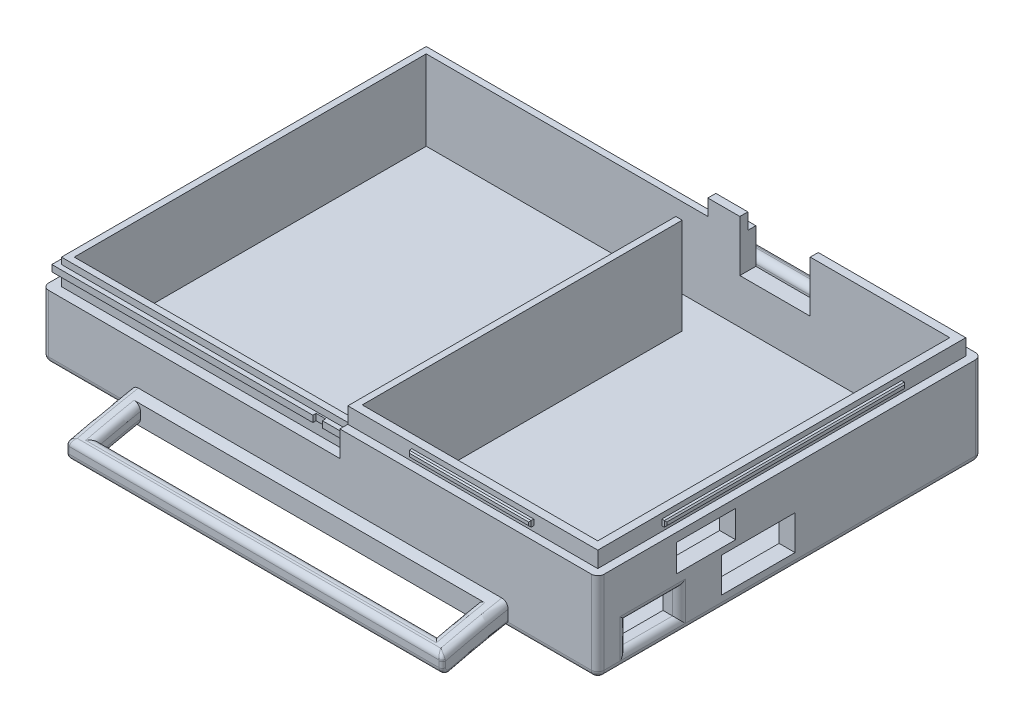
SolidWorks part; units mm, degrees
ref_plane "Front Plane" through (0, 0, 0) normal (0, 0, 1) x (1, 0, 0)
ref_plane "Top Plane" through (0, 0, 0) normal (0, 1, 0) x (1, 0, 0)
ref_plane "Right Plane" through (0, 0, 0) normal (1, 0, 0) x (0, 0, -1)
sketch "Sketch1" plane through (0, 0, 0) normal (0, 1, 0) x (1, 0, 0)
  line L1 (22, -27.5) -> (-22, -27.5)
  line L2 (22, -27.5) -> (22, 27.5)
  line L3 (22, 27.5) -> (-22, 27.5)
  line L4 (-22, -27.5) -> (-22, 27.5)
  line L5 (22, -27.5) -> (-22, 27.5) construction
  line L6 (22, 27.5) -> (-22, -27.5) construction
  line L10 (23, 27.5) -> (23, -27.5)
  line L11 (23, 27.5) -> (59.8, 27.5)
  line L12 (23, -27.5) -> (59.8, -27.5)
  line L13 (59.8, 27.5) -> (59.8, -27.5)
  line L14 (22, 27.5) -> (22, -27.5)
  line L15 (22, 27.5) -> (23, 27.5)
  line L16 (22, -27.5) -> (23, -27.5)
  line L17 (23, 27.5) -> (23, -27.5)
  line L18 (22, -30) -> (-24.5, -30)
  line L19 (-24.5, -30) -> (-24.5, 30)
  line L20 (22, 30) -> (-24.5, 30)
  line L21 (22, 30) -> (23, 30)
  line L22 (23, 30) -> (62.3, 30)
  line L23 (62.3, 30) -> (62.3, -30)
  line L24 (23, -30) -> (62.3, -30)
  line L25 (22, -30) -> (23, -30)
  line L26 (22, 30) -> (22, 27.5)
  line L27 (22, -27.5) -> (22, -30)
  line L29 (22, 27.5) -> (23, 27.5)
  line L30 (22, 27.5) -> (22, -27.5)
  line L31 (22, -27.5) -> (23, -27.5)
  line L32 (23, 27.5) -> (23, -27.5)
  line L33 (22, 27.5) -> (23, 27.5)
  line L34 (22, 27.5) -> (22, 22.5)
  line L35 (22, 22.5) -> (23, 22.5)
  line L36 (23, 27.5) -> (23, 22.5)
  point P0 (0, 0)
  dimension "D1" = 55
  dimension "D2" = 44
  dimension "D3" = 1
  dimension "D4" = 2.5
  dimension "D5" = 86.8
  dimension "D6" = 36.8
  dimension "D7" = 60
  dimension "D8" = 5
extrude "Boss-Extrude1" add sketch "Sketch1" along normal blind 12.5 contours L27 L1 L4 L3 L26 L20 L19 L18 region at (21.2409, 0, 28.75)
extrude "Boss-Extrude2" add sketch "Sketch1<5>" along normal blind 15 contours L16 L27 L25 L24 L23 L22 L21 L26 L15 L11 L13 L12 region at (22.5, 0, 28.2228)
sketch "Sketch1<5>" plane through (0, 0, 0) normal (0, 1, 0) x (1, 0, 0) same geometry as "Sketch1"
extrude "Boss-Extrude3" add sketch "Sketch1<7>" along normal blind 15 contours L2 L16 L10 L15 region at (22.5, 0, 2.5)
sketch "Sketch1<7>" plane through (0, 0, 0) normal (0, 1, 0) x (1, 0, 0) same geometry as "Sketch1"
extrude "Boss-Extrude5" add sketch "Sketch1<10>" against normal blind 1.5 contours L27 L1 L4 L3 L26 L20 L19 L18 | L4 L1 L2 L3 | L13 L11 L10 L12 | L2 L16 L10 L15 | L16 L27 L25 L24 L23 L22 L21 L26 L15 L11 L13 L12 | L30 L35 L10 L15 region at (21.2409, 0, 28.75) region at (0, 0, 0) region at (22.5, 0, 2.5) region at (22.5, 0, 28.2228) region at (22.5, 0, -25) region at (41.4, 0, 0)
sketch "Sketch1<10>" plane through (0, 0, 0) normal (0, 1, 0) x (1, 0, 0) same geometry as "Sketch1"
sketch "Sketch2" plane through (62.3, 0, 0) normal (1, 0, 0) x (0, 0, -1)
  line L0 (-25.5, 0.5) -> (-17.3172, 0.5)
  line L1 (-25.5, 0.5) -> (-25.5, 4.5)
  line L2 (-25.5, 4.5) -> (-17.3172, 4.5)
  line L3 (-17.3172, 0.5) -> (-17.3172, 4.5)
  line L4 (-10.6702, 0.4971) -> (-10.6702, 5.8971)
  line L5 (-10.6702, 5.8971) -> (0.8298, 5.8971)
  line L6 (0.8298, 0.4971) -> (0.8298, 5.8971)
  line L7 (-10.6702, 0.4971) -> (0.8298, 0.4971)
  line L8 (-17.6602, 6.8853) -> (-8.4602, 6.8853)
  line L9 (-17.6602, 6.8853) -> (-17.6602, 11.1353)
  line L10 (-17.6602, 11.1353) -> (-8.4602, 11.1353)
  line L11 (-8.4602, 6.8853) -> (-8.4602, 11.1353)
  line L12 (-30, 15) -> (-30, -1.5) construction
  line L14 (30, -1.5) -> (-30, -1.5) construction
  dimension "D1" = 0.9882
  dimension "D2" = 2.3853
  dimension "D3" = 9.2
  dimension "D4" = 2.21
  dimension "D5" = 0.343
  dimension "D6" = 4.5
  dimension "D7" = 4
  dimension "D8" = 4.25
  dimension "D9" = 2
  dimension "D10" = 11.5
extrude "Side_USB" cut sketch "Sketch2" against normal blind 10
sketch "Sketch3" plane through (0, 0, -30) normal (0, 0, -1) x (-1, 0, 0)
  line L0 (-22, 15) -> (-22, 12.5) construction
  line L1 (-38, 15) -> (-27, 15)
  line L2 (-38, 15) -> (-38, 7)
  line L3 (-38, 7) -> (-27, 7)
  line L4 (-27, 15) -> (-27, 7)
  line L5 (-22, 15) -> (-62.3, 15) construction
  dimension "D1" = 5
  dimension "D2" = 0
  dimension "D3" = 8
  dimension "D4" = 11
extrude "Back_USB" cut sketch "Sketch3" against normal blind 10
sketch "Sketch4" plane through (0, 15, 0) normal (0, 1, 0) x (1, 0, 0)
  line L0 (23.25, -28.75) -> (23.25, 28.75)
  line L1 (22, -30) -> (62.3, -30)
  line L2 (22, -30) -> (22, 30)
  line L3 (22, 30) -> (62.3, 30)
  line L4 (62.3, -30) -> (62.3, 30)
  line L5 (23.25, 28.75) -> (61.05, 28.75)
  line L6 (61.05, -28.75) -> (61.05, 28.75)
  line L7 (23.25, -28.75) -> (61.05, -28.75)
  line L8 (22, 27.5) -> (23.25, 27.5)
  line L9 (59.8, 27.5) -> (-22, 27.5) construction
  line L10 (22, 27.5) -> (27, 27.5) construction
  line L11 (22, -27.5) -> (23.25, -27.5)
  line L12 (59.8, -27.5) -> (23, -27.5) construction
  line L13 (23.25, 28.75) -> (22, 28.75)
  line L14 (23.25, -28.75) -> (22, -28.75)
  line M9 (38, 30) -> (38, 27.5)
  line M15 (22, 22.5) -> (22, -30)
  line M16 (22, -30) -> (62.3, -30)
  line M17 (62.3, -30) -> (62.3, 30)
  line M18 (62.3, 30) -> (38, 30)
  dimension "D1" = 1.25
extrude "Groove" cut sketch "Sketch4" against normal blind 2.5 contours L7 L14 L5 L6 M15 M16 M17 M18 M9 | L13 L5 L3 L2 M9 region at (42.15, 15, 29.4728) region at (30, 15, -29.375)
sketch "LidGrip_Back_Sketch" plane through (0, 0, -28.75) normal (0, 0, -1) x (-1, 0, 0)
  line L0 (-38, 15) -> (-61.05, 15) construction
  line L1 (-58.05, 14.2) -> (-41, 14.2)
  line L2 (-58.05, 14.2) -> (-58.05, 13.3)
  line L3 (-58.05, 13.3) -> (-41, 13.3)
  line L4 (-41, 14.2) -> (-41, 13.3)
  line L5 (-62.3, 12.5) -> (-38, 12.5) construction
  line L6 (-38, 15) -> (-38, 12.5) construction
  line L7 (-61.05, 12.5) -> (-61.05, 15) construction
  dimension "D1" = 0.8
  dimension "D2" = 0.8
  dimension "D3" = 3
  dimension "D4" = 3
  dimension "D5" = 0.9
  dimension "D6" = 17.05
sketch "LidGrip_Side_Sketch" plane through (61.05, 0, 0) normal (1, 0, 0) x (0, 0, -1)
  line L0 (-28.75, 12.5) -> (-28.75, 15) construction
  line L1 (-18.75, 14.2) -> (18.75, 14.2)
  line L2 (-18.75, 14.2) -> (-18.75, 13.3)
  line L3 (-18.75, 13.3) -> (18.75, 13.3)
  line L4 (18.75, 14.2) -> (18.75, 13.3)
  line L5 (28.75, 12.5) -> (28.75, 15) construction
  line L6 (-28.75, 15) -> (28.75, 15) construction
  line L7 (-28.75, 12.5) -> (28.75, 12.5) construction
  dimension "D1" = 10
  dimension "D2" = 10
  dimension "D3" = 0.8
  dimension "D4" = 0.8
sketch "LidGrip_Front_Sketch" plane through (0, 0, 28.75) normal (0, 0, 1) x (1, 0, 0)
  line L1 (32, 14.2) -> (51.05, 14.2)
  line L2 (32, 14.2) -> (32, 13.3)
  line L3 (32, 13.3) -> (51.05, 13.3)
  line L4 (51.05, 14.2) -> (51.05, 13.3)
  line L5 (22, 12.5) -> (22, 15) construction
  line L6 (61.05, 12.5) -> (61.05, 15) construction
  line L7 (22, 15) -> (61.05, 15) construction
  line L8 (-24.5, 12.5) -> (62.3, 12.5) construction
  dimension "D1" = 10
  dimension "D2" = 10
  dimension "D3" = 0.8
  dimension "D4" = 0.8
extrude "LidGrip_Back" add sketch "LidGrip_Back_Sketch" along normal blind 0.6
extrude "LidGrip_Front" add sketch "LidGrip_Front_Sketch" along normal blind 0.6
extrude "LidGrip_Side" add sketch "LidGrip_Side_Sketch" along normal blind 0.6
chamfer "LidGrip_Back_Chamfer" distance 0.2 angle 45 4 edges at (49.525, 14.2, -29.35) (41, 13.75, -29.35) (49.525, 13.3, -29.35) (58.05, 13.75, -29.35)
chamfer "LidGrip_Front_Chamfer" distance 0.2 angle 45 4 edges at (41.525, 14.2, 29.35) (51.05, 13.75, 29.35) (41.525, 13.3, 29.35) (32, 13.75, 29.35)
chamfer "LidGrip_Side_Chamfer" distance 0.2 angle 45 4 edges at (61.65, 14.2, 0) (61.65, 13.75, -18.75) (61.65, 13.3, 0) (61.65, 13.75, 18.75)
sketch "Sketch5" plane through (-24.5, 0, 0) normal (-1, 0, 0) x (0, 0, 1)
  line L0 (-28.5, 12.5) -> (-28.5, 10.5)
  line L1 (-30, 12.5) -> (-28.5, 12.5)
  line L2 (-30, 12.5) -> (-30, 8.5)
  line L3 (-30, 8.5) -> (-28.5, 8.5)
  line L5 (-30, 10.5) -> (-28.5, 10.5)
  line L6 (-30, 10.5) -> (-30, 8.5)
  line L7 (-30, 8.5) -> (-28.5, 8.5)
  line L8 (-28.5, 10.5) -> (-28.5, 8.5)
  line L9 (-29.25, 12.5) -> (-29.25, 10.5)
  line L10 (30, 12.5) -> (-30, 12.5) construction
  line L11 (-29.25, 11.5) -> (0, 11.5)
  line L12 (-29.25, 11.5) -> (-29.25, 12.5)
  line L13 (-29.25, 12.5) -> (0, 12.5)
  line L14 (0, 11.5) -> (0, 12.5)
  line L16 (-28.5, 11.5) -> (0, 11.5)
  line L17 (-28.5, 11.5) -> (-28.5, 8.5)
  line L18 (-28.5, 8.5) -> (0, 8.5)
  line L19 (0, 11.5) -> (0, 8.5)
  line L20 (-28.5, 10.5) -> (0, 10.5)
  line L21 (-28.5, 10.5) -> (-28.5, 11.5)
  line L22 (-28.5, 11.5) -> (0, 11.5)
  line L23 (0, 10.5) -> (0, 11.5)
  line M7 (-30, 12.5) -> (-30, -1.5)
  line M10 (30, 12.5) -> (-30, 12.5)
  dimension "D1" = 2
  dimension "D2" = 1.5
  dimension "D3" = 2
extrude "Cut-Extrude3" cut sketch "Sketch5" against normal blind 46.5 contours L8 L5 L2 L3 | L9 L1 L5 M7 | L9 L11 L0 M10 region at (-24.5, 12, -28.875) region at (-24.5, 11.5, -29.625) region at (-24.5, 9.5, -29.25)
extrude "Cut-Extrude4" cut sketch "Sketch5<5>" against normal blind 1.5 contours L11 L14 L0 M10 region at (-24.5, 12, -14.25)
sketch "Sketch5<5>" plane through (-24.5, 0, 0) normal (-1, 0, 0) x (0, 0, 1) same geometry as "Sketch5"
ref_plane "Plane1" through (0, 0, 0) normal (0, 0, 1) x (1, 0, 0)
extrude "Cut-Extrude5" cut sketch "Sketch5<6>" against normal blind 0.75 contours L0 L20 L19 L11 | L11 L9 L5 L0 region at (-24.5, 11, -14.25) region at (-24.5, 11, -28.875)
sketch "Sketch5<6>" plane through (-24.5, 0, 0) normal (-1, 0, 0) x (0, 0, 1) same geometry as "Sketch5"
extrude "Cut-Extrude6" cut sketch "Sketch5<7>" against normal blind 1.5 contours L20 L8 L18 L19 region at (-24.5, 9.5, -14.25)
sketch "Sketch5<7>" plane through (-24.5, 0, 0) normal (-1, 0, 0) x (0, 0, 1) same geometry as "Sketch5"
mirror "Mirror2" about plane through (0, 0, 0) normal (0, 0, 1) of "Cut-Extrude6", "Cut-Extrude5", "Cut-Extrude4", "Cut-Extrude3"
sketch "Sketch6" plane through (62.3, 0, 0) normal (1, 0, 0) x (0, 0, -1)
  line L0 (30, -1.5) -> (-30, -1.5) construction
  line L1 (-30, 12.5) -> (-30, -1.5) construction
  line L2 (-30, 2.8883) -> (-40.2913, 2.8883)
  line L3 (-30, 2.8883) -> (-30, -3.7013)
  line L4 (-30, -3.7013) -> (-40.2913, -3.7013)
  line L5 (-40.2913, 2.8883) -> (-40.2913, -3.7013)
  circle A0 centre (0, -161.5) radius 163.5
  circle A1 centre (0, -161.5) radius 166.5
  point P4 (0, -1.5)
  dimension "D2" = 3
  dimension "D1" = 160
extrude "Boss-Extrude6" add sketch "Sketch6" against normal blind 86.8 contours L3 A1 L5 A0 region at (62.3, -0.3182, 35.1576)
sketch "Sketch7" plane through (0, 12.5, 0) normal (0, 1, 0) x (1, 0, 0)
  line L1 (-7.5, -31.6584) -> (45.3, -31.6584)
  line L2 (-7.5, -31.6584) -> (-7.5, -37.9718)
  line L3 (-7.5, -37.9718) -> (45.3, -37.9718)
  line L4 (45.3, -31.6584) -> (45.3, -37.9718)
  line L6 (22, -30) -> (-24.5, -30) construction
  line L7 (-24.5, -40.2913) -> (-10.5, -40.2913)
  line L8 (-24.5, -40.2913) -> (-24.5, -30)
  line L9 (-24.5, -30) -> (-10.5, -30)
  line L10 (-10.5, -40.2913) -> (-10.5, -30)
  line L11 (62.3, -30) -> (22, -30) construction
  line L12 (62.3, -40.2913) -> (48.3, -40.2913)
  line L13 (62.3, -40.2913) -> (62.3, -30)
  line L14 (62.3, -30) -> (48.3, -30)
  line L15 (48.3, -40.2913) -> (48.3, -30)
  dimension "D2" = 14
  dimension "D3" = 52.8
  dimension "D4" = 14
extrude "Cut-Extrude7" cut sketch "Sketch7" against normal blind 20
mirror "Mirror3" about plane through (0, 0, 0) normal (0, 0, 1) of "Boss-Extrude6", "Cut-Extrude7"
fillet "Fillet1" radius 1 33 edges at (62.3, 2.5, 17.3172) (62.3, 0.5, 21.4086) (62.3, 2.5, 25.5) (62.3, 4.5, 21.4086) (18.9, -2.4705, -37.9718) (-7.5, -1.7512, -34.8219) (18.9, -3.0422, -40.2913) (-10.5, 1.2446, -35.1632) (48.3, 1.2446, -35.1632) (18.9, 0.0514, -40.2913) (45.3, -1.7512, -34.8219) (45.3, 1.318, -34.8217) (18.9, 1.9625, -31.6584) (-7.5, 1.318, -34.8217) (18.9, 0.6123, -37.9718) (18.9, -2.4705, 37.9718) (45.3, -1.7512, 34.8219) (45.3, 1.318, 34.8217) (18.9, 0.6123, 37.9718) (-7.5, 1.318, 34.8217) (-7.5, -1.7512, 34.8219) (18.9, -3.0422, 40.2913) (18.9, 0.0514, 40.2913) (-10.5, 1.2446, 35.1632) (48.3, 1.2446, 35.1632) (62.3, 5.5, 30) (-24.5, 3.5, 30) (-24.5, 3.5, -30) (62.3, 5.5, -30) (18.9, -1.5, -30) (-24.5, -1.5, 0) (18.9, -1.5, 30) (62.3, -1.5, 0)
fillet "Fillet2" radius 0.5 20 edges at (-10.1458, -0.145, 40.1011) (-10.5, -1.3704, 40.2913) (-10.5, -2.5484, 39.9082) (47.9458, -0.145, 40.1011) (48.3, -1.3704, 40.2913) (48.3, -2.5484, 39.9082) (47.9458, -0.145, -40.1011) (48.3, -1.3704, -40.2913) (48.3, -2.5484, -39.9082) (-10.1458, -0.145, -40.1011) (-10.5, -1.3704, -40.2913) (-10.5, -2.5484, -39.9082) (-10.5, -1.6861, 34.5218) (48.3, -1.6861, 34.5218) (48.3, -1.6861, -34.5218) (-10.5, -1.6861, -34.5218)
sketch "Sketch8" plane through (0, 0, -29.25) normal (0, 0, -1) x (-1, 0, 0)
  line L0 (-22, 11.5) -> (23.75, 11.5) construction
  line L1 (-18.5357, 11.5) -> (-17.0357, 11.5)
  line L2 (-18.5357, 11.5) -> (-18.5357, 10.5)
  line L3 (-18.5357, 10.5) -> (-17.0357, 10.5)
  line L4 (-17.0357, 11.5) -> (-17.0357, 10.5)
  line L5 (-18.5357, 11.5) -> (-18.5357, 10.5) construction
  line L6 (-22, 10.5) -> (23.75, 10.5) construction
  line L7 (-17.0357, 10.5) -> (-17.0357, 11.5) construction
extrude "Cut-Extrude8" cut sketch "Sketch8" against normal blind 0.5
mirror "Mirror4" about plane through (0, 0, 0) normal (0, 0, 1) of "Cut-Extrude8"
